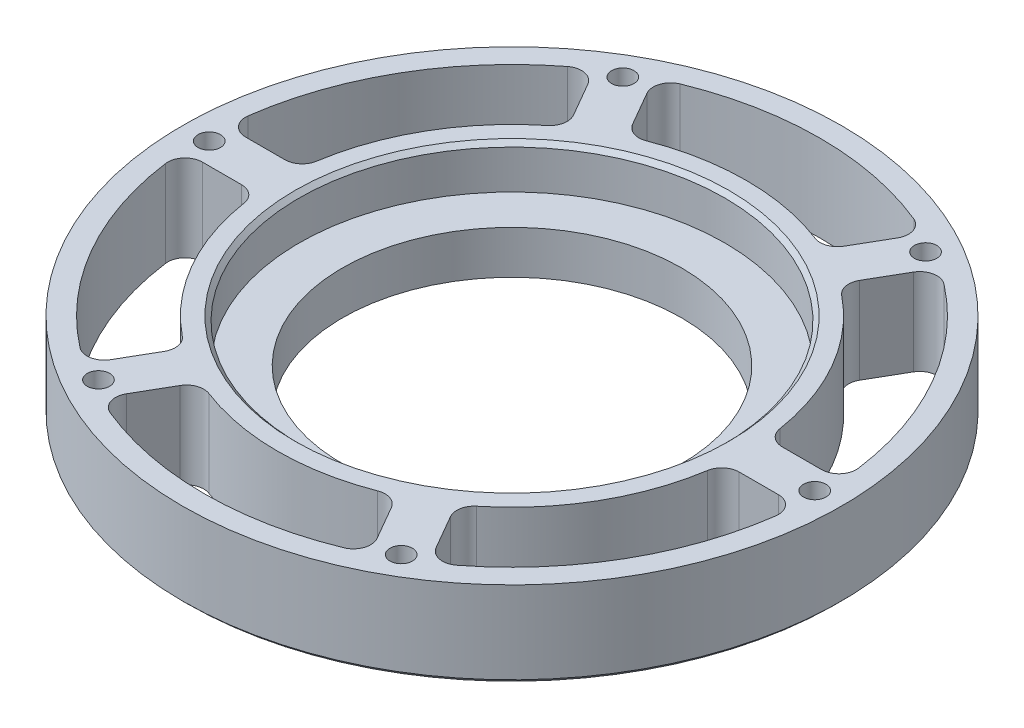
SolidWorks part; units mm, degrees
material "6061-T6 (SS)"
ref_plane "Front Plane" through (0, 0, 0) normal (0, 0, 1) x (1, 0, 0)
ref_plane "Top Plane" through (0, 0, 0) normal (0, 1, 0) x (1, 0, 0)
ref_plane "Right Plane" through (0, 0, 0) normal (1, 0, 0) x (0, 0, -1)
sketch "Sketch2" plane through (0, 0, 0) normal (1, 0, 0) x (0, 0, -1)
  line L0 (-39.2125, 0) -> (-76.2, 0)
  line L1 (-76.2, 0) -> (-76.2, 20)
  line L2 (-76.2, 20) -> (-49.2125, 20)
  line L3 (-49.2125, 20) -> (-49.2125, 10)
  line L4 (-49.2125, 10) -> (-39.2125, 10)
  line L5 (-39.2125, 10) -> (-39.2125, 0)
  dimension "D1" = 76.2
  dimension "D2" = 20
  dimension "D3" = 10
  dimension "D4" = 49.2125
  dimension "D5" = 10
ref_axis "Axis1" through (0, -1, 0) along (0, 1, 0)
revolve "Revolve1" add sketch "Sketch2" angle 360 about axis through (0, -1, 0) along (0, 1, 0)
hole_wizard "#6 (0.204) Diameter Hole1" positions "Sketch6" profile "Sketch7" hole size "#6" standard "ANSI Inch" end condition through all
sketch "Sketch6" plane through (0, 20, 0) normal (0, 1, 0) x (1, 0, 0)
  line L0 (0, 0) -> (-69.8201, 120.932) construction
  line L2 (0, 0) -> (0, 109.0908) construction
  point P0 (-35, 60.6218)
  dimension "D1" = 30
  dimension "D2" = 70
sketch "Sketch7" plane through (-35, 20, -60.6218) normal (1, 0, 0) x (0, 0, 1)
  line L0 (0, 0) -> (0, 20)
  line L1 (0, 20) -> (2.5908, 20)
  line L2 (2.5908, 20) -> (2.5908, 0)
  line L5 (2.5908, 0) -> (0, 0)
  line L11 (0, -6.35) -> (0, 107.95) construction
  dimension "Thru Hole Dia." = 5.1816
  dimension "Thru Hole Depth" = 20
pattern_circular "CirPattern3" count 6 over 360 about axis through (0, -1, 0) along (0, 1, 0) of "#6 (0.204) Diameter Hole1"
sketch "Sketch8" plane through (0, 20, 0) normal (0, 1, 0) x (1, 0, 0)
  line L0 (-31.182, 64.0088) -> (-22.6606, 49.2493)
  line L1 (31.182, 64.0088) -> (22.6606, 49.2493)
  line L2 (0, 0) -> (-35, 60.6218) construction
  line L4 (0, 0) -> (0, 93.9995) construction
  arc A0 (-22.6606, 49.2493) -> (22.6606, 49.2493) centre (0, 0) cw
  arc A1 (-31.182, 64.0088) -> (31.182, 64.0088) centre (0, 0) cw
  circle A2 centre (0, 0) radius 49.2125 construction
  circle A3 centre (0, 0) radius 76.2 construction
  dimension "D1" = 5
  dimension "D2" = 5
  dimension "D3" = 5
extrude "Cut-Extrude1" cut sketch "Sketch8" against normal through all
fillet "Fillet1" radius 4 4 edges at (31.182, 10, -64.0088) (22.6606, 10, -49.2493) (-31.182, 10, -64.0088) (-22.6606, 10, -49.2493)
pattern_circular "CirPattern4" count 6 over 360 about axis through (0, -1, 0) along (0, 1, 0) of "Cut-Extrude1", "Fillet1"
chamfer "Chamfer1" distance 1 angle 45 1 edges at (0, 20, -49.2125)
chamfer "Chamfer2" distance 1 angle 45 1 edges at (0, 0, -76.2)
equation "\"TubeDiameter\"= 6.000in"
equation "\"D1@Sketch2\"=\"TubeDiameter\"/2"
